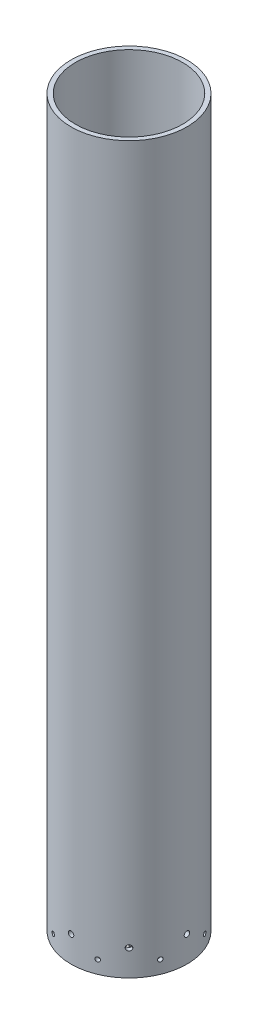
SolidWorks part; units mm, degrees
material "Acrylic (Medium-high impact)"
ref_plane "Front Plane" through (0, 0, 0) normal (0, 0, 1) x (1, 0, 0)
ref_plane "Top Plane" through (0, 0, 0) normal (0, 1, 0) x (1, 0, 0)
ref_plane "Right Plane" through (0, 0, 0) normal (1, 0, 0) x (0, 0, -1)
sketch "Sketch1" plane through (0, 0, 0) normal (0, 1, 0) x (1, 0, 0)
  circle A0 centre (0, 0) radius 40
  circle A1 centre (0, 0) radius 36.95
  dimension "D1" = 73.9
  dimension "D2" = 80
extrude "Boss-Extrude1" add sketch "Sketch1" along normal blind 500
sketch "Sketch2" plane through (0, 0, 0) normal (0, 0, 1) x (1, 0, 0)
  line L4 (0, 0) -> (0, 35)
  circle A0 centre (0, 18) radius 1.9
  point P10 (0, 26)
  point P11 (0, 18)
  dimension "D4" = 35
  dimension "D1" = 3.8
  dimension "D5" = 9
  dimension "D6" = 8
extrude "Cut-Extrude1" cut sketch "Sketch2" against normal blind 66 contours A0
sketch "Sketch3" plane through (0, 0, 0) normal (0, -1, 0) x (1, 0, 0)
  line L0 (0, 0) -> (0, -21.7029)
  line L1 (0, 0) -> (-8.4387, -20.3728)
  line L2 (-8.4387, -20.3728) -> (0, -21.7029)
  dimension "D1" = 22.5
extrude "Boss-Extrude2" add sketch "Sketch3" along normal blind 10 and the other way blind 18 separate body
sketch "Sketch4" plane through (0, 0, 0) normal (-0.9239, 0, 0.3827) x (0.3827, 0, 0.9239)
  line L0 (0, 18) -> (-22.0514, 18) construction
  circle A0 centre (0, 9) radius 1.5
  dimension "D1" = 9
extrude "Cut-Extrude2" cut sketch "Sketch4" against normal blind 68
pattern_circular "CirPattern1" count 8 over 360 about axis through (0, 500, 0) along (0, -1, 0) of "Cut-Extrude1", "Cut-Extrude2"
split line "Split Line2"
sketch "Sketch7" plane through (0, 18, 0) normal (0, 1, 0) x (1, 0, 0)
  circle A0 centre (-3.3193, 15.2362) radius 1
extrude "Boss-Extrude3" add sketch "Sketch7" along normal blind 10
split line "Split Line3"
